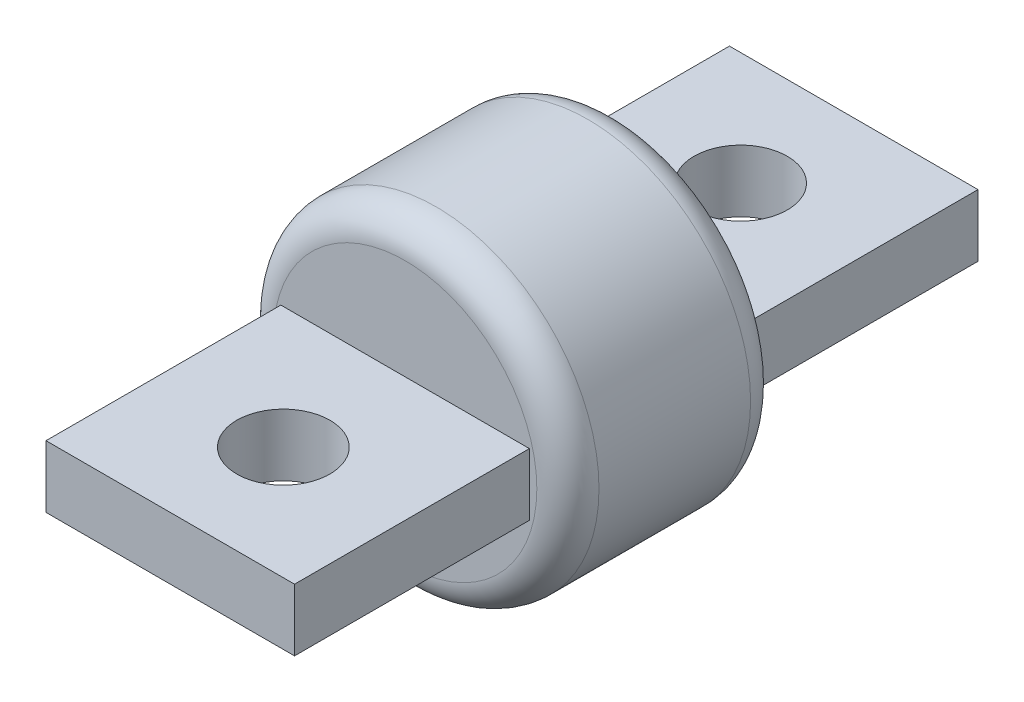
SolidWorks part; units mm, degrees
ref_plane "Front Plane" through (0, 0, 0) normal (0, 0, 1) x (1, 0, 0)
ref_plane "Top Plane" through (0, 0, 0) normal (0, 1, 0) x (1, 0, 0)
ref_plane "Right Plane" through (0, 0, 0) normal (1, 0, 0) x (0, 0, -1)
sketch "Sketch1" plane through (0, 0, 0) normal (0, 0, 1) x (1, 0, 0)
  circle A0 centre (0, 0) radius 16.637
  dimension "D1" = 33.274
extrude "Boss-Extrude1" add sketch "Sketch1" along normal blind 21.844
sketch "Sketch2" plane through (0, 0, 21.844) normal (0, 0, 1) x (1, 0, 0)
  line L1 (-12.7, -3.175) -> (12.7, -3.175)
  line L2 (-12.7, -3.175) -> (-12.7, 3.175)
  line L3 (-12.7, 3.175) -> (12.7, 3.175)
  line L4 (12.7, -3.175) -> (12.7, 3.175)
  line L5 (-12.7, -3.175) -> (12.7, 3.175) construction
  line L6 (-12.7, 3.175) -> (12.7, -3.175) construction
  point P0 (0, 0)
  dimension "D1" = 6.35
  dimension "D2" = 25.4
extrude "Boss-Extrude2" add sketch "Sketch2" along normal blind 24.003
sketch "Sketch3" plane through (0, 0, 0) normal (0, 0, -1) x (-1, 0, 0)
  line L1 (12.7, -3.175) -> (-12.7, -3.175)
  line L2 (12.7, -3.175) -> (12.7, 3.175)
  line L3 (12.7, 3.175) -> (-12.7, 3.175)
  line L4 (-12.7, -3.175) -> (-12.7, 3.175)
  line L5 (12.7, -3.175) -> (-12.7, 3.175) construction
  line L6 (12.7, 3.175) -> (-12.7, -3.175) construction
  point P0 (0, 0)
  dimension "D1" = 25.4
  dimension "D2" = 6.35
extrude "Boss-Extrude3" add sketch "Sketch3" along normal blind 24.003
sketch "Sketch4" plane through (0, 3.175, 0) normal (0, 1, 0) x (1, 0, 0)
  line L0 (0, 24.003) -> (0, -45.847) construction
  line L1 (-12.7, 24.003) -> (12.7, 24.003) construction
  line L2 (12.7, -45.847) -> (-12.7, -45.847) construction
  line L3 (0, 24.003) -> (0, 12.446) construction
  line L4 (0, -45.847) -> (0, -34.29) construction
  circle A0 centre (0, 12.446) radius 4.7625
  circle A1 centre (0, -34.29) radius 4.7625
  point P12 (0, 12.446)
  point P13 (0, -34.29)
  point P20 (0, -10.922)
  point P22 (0, -10.922)
  dimension "D2" = 9.525
  dimension "D1" = 46.736
  dimension "D3" = 69.85
extrude "Cut-Extrude1" cut sketch "Sketch4" against normal through all contours A0 | A1
ref_axis "Axis1" through (0, -3.175, 34.29) along (0, 1, 0)
ref_axis "Axis2" through (0, -3.175, -12.446) along (0, 1, 0)
fillet "Fillet1" radius 3.175 2 edges at (16.637, 0, 0) (16.637, 0, 21.844)
sketch3d "3DSketch1"
  line L0 (0, 0, 34.29) -> (0, 0, -12.446) construction
  line L1 (0, -3.175, 34.29) -> (0, 3.175, 34.29) construction
  line L2 (0, -3.175, -12.446) -> (0, 3.175, -12.446) construction
  line L3 (0, 0, 34.29) -> (0, 3.175, 34.29) construction
  line L4 (0, 0, 34.29) -> (0, -3.175, 34.29) construction
  line L5 (0, 0, -12.446) -> (0, 3.175, -12.446) construction
  line L6 (0, 0, -12.446) -> (0, -3.175, -12.446) construction
  point P9 (0, 0, 34.29)
  point P11 (0, 0, 0)
